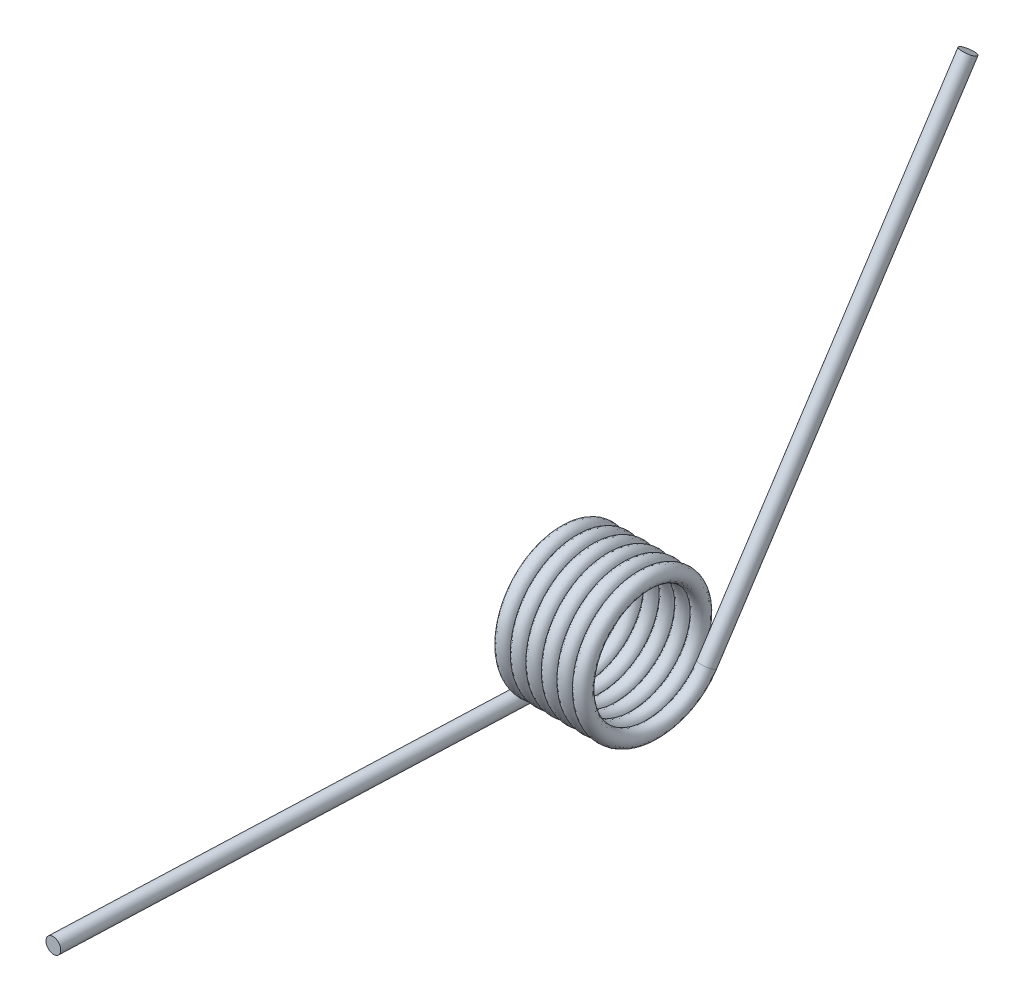
SolidWorks part; units mm, degrees
ref_plane "Front" through (0, 0, 0) normal (0, 0, 1) x (1, 0, 0)
ref_plane "Top" through (0, 0, 0) normal (0, 1, 0) x (1, 0, 0)
ref_plane "Right" through (0, 0, 0) normal (1, 0, 0) x (0, 0, -1)
sketch "Sketch1" plane through (0, 0, 0) normal (1, 0, 0) x (0, 0, -1)
  line L0 (0, -8.6487) -> (0, -11.0617) construction
  line L1 (9.5797, -5.5309) -> (47.6797, 60.4603) construction
  line L2 (0, -11.0617) -> (-76.2, -11.0617) construction
  line L3 (0, 0) -> (11.0617, 0) construction
  line L4 (0, 0) -> (9.5797, -5.5309) construction
  line L5 (-76.2, -11.0617) -> (-76.2, -8.6487) construction
  line L6 (-76.2, -8.6487) -> (0, -8.6487) construction
  line L7 (47.6797, 60.4603) -> (45.59, 61.6668) construction
  line L8 (45.59, 61.6668) -> (7.49, -4.3244) construction
  circle A0 centre (0, 0) radius 11.0617 construction
  circle A1 centre (0, 0) radius 7.9375 construction
  circle A2 centre (0, 0) radius 9.8552 construction
  point P7 (0, -9.8552)
  point P10 (0, 11.0617)
  dimension "OD" = 22.1234
  dimension "For Shaft Diameter" = 15.875
  dimension "Wire Diameter" = 2.413
  dimension "Leg Length" = 76.2
  dimension "Deflection Angle" = 120
sketch "Sketch2" plane through (0, 0, 0) normal (1, 0, 0) x (0, 0, -1)
  circle A0 centre (0, 0) radius 9.8552 construction
  circle A2 centre (0, 0) radius 9.8552
curve "Helix/Spiral1" pitch 2.4384 height 15.0368 radius 9.8552 centre (0, 0, 0) axis (1, 0, 0) start towards (0, 0, -1)
ref_plane "Plane1" through (0, -9.8552, 0) normal (0.0393, 0, -0.9992) x (0.999, -0.0232, 0.0393)
sketch "Sketch3" plane through (0, -9.8552, 0) normal (0.0393, 0, -0.9992) x (0.999, -0.0232, 0.0393)
  circle A0 centre (0, 0) radius 1.2065
  dimension "D1" = 2.413
sweep "Sweep1" add profiles "Sketch3" path "Helix/Spiral1"
sketch "Sketch4" plane through (0, 0, 0) normal (-0.0393, 0, 0.9992) x (-0.999, 0.0232, -0.0393)
  circle A1 centre (-0.229, 9.8525) radius 1.2065
  circle A2 centre (-0.229, 9.8525) radius 1.2065
  dimension "D1" = 0
extrude "Extrude1" add sketch "Sketch4" along normal blind 76.2
sketch "Sketch5" plane through (0.0233, 0.512, -0.2956) normal (0.0393, 0.8654, -0.4996) x (0.9982, -0.0569, -0.02)
  circle A1 centre (15.4605, 9.1571) radius 1.2065
  circle A2 centre (15.4605, 9.1571) radius 1.2065
  dimension "D1" = 0
extrude "Extrude2" add sketch "Sketch5" along normal blind 76.2
sketch "Sketch6" plane through (0, 0, 0) normal (1, 0, 0) x (0, 0, -1)
  circle A2 centre (0, 0) radius 8.6487 construction
sketch "Sketch8" plane through (0, 0, 0) normal (1, 0, 0) x (0, 0, -1)
  circle A0 centre (0, 0) radius 11.3576
equation "\"D4@Helix/Spiral1\" = \"Wire Diameter@Sketch1\" + .001"
equation "\"D1@Sketch3\"=\"Wire Diameter@Sketch1\""
equation "\"D1@Extrude2\"=\"Leg Length@Sketch1\""
equation "\"Leg Length@Extrude1\"=\"Leg Length@Sketch1\""
